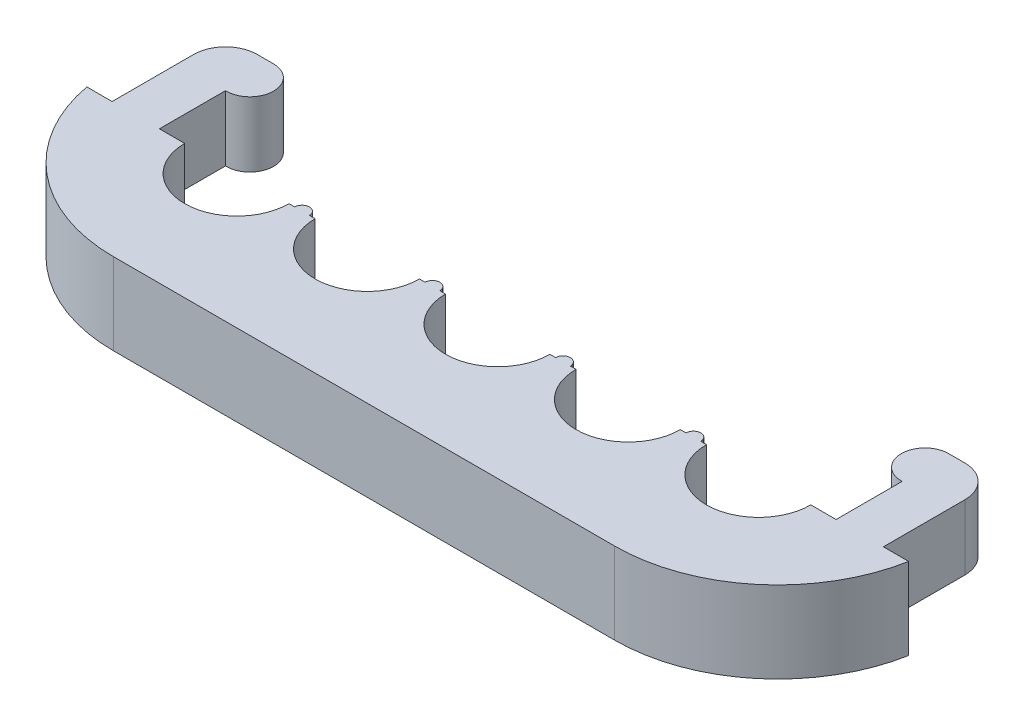
SolidWorks part; units mm, degrees
ref_plane "Plano frontal" through (0, 0, 0) normal (0, 0, 1) x (1, 0, 0)
ref_plane "Plano superior" through (0, 0, 0) normal (0, 1, 0) x (1, 0, 0)
ref_plane "Plano direito" through (0, 0, 0) normal (1, 0, 0) x (0, 0, -1)
sketch "Esboço1" plane through (0, 0, 0) normal (0, 1, 0) x (1, 0, 0)
  line L0 (-25.2, 0) -> (-19.2, 0)
  line L5 (25.2, 0) -> (25.2, -8.2)
  line L6 (25.2, -8.2) -> (-25.2, -8.2)
  line L7 (-25.2, -8.2) -> (-25.2, 0)
  line L8 (-12.8, 0) -> (-11.2, 0)
  line L9 (-4.8, 0) -> (-3.2, 0)
  line L10 (3.2, 0) -> (4.8, 0)
  line L11 (11.2, 0) -> (12.8, 0)
  line L12 (19.2, 0) -> (25.2, 0)
  arc A0 (-19.2, 0) -> (-12.8, 0) centre (-16, 0) ccw
  arc A1 (-11.2, 0) -> (-4.8, 0) centre (-8, 0) ccw
  arc A2 (-3.2, 0) -> (3.2, 0) centre (0, 0) ccw
  arc A3 (4.8, 0) -> (11.2, 0) centre (8, 0) ccw
  arc A4 (12.8, 0) -> (19.2, 0) centre (16, 0) ccw
  dimension "D1" = 6.4
  dimension "D4" = 6
  dimension "D5" = 5
  dimension "D3" = 8
  dimension "D2" = 5
extrude "Ressalto-extrusão1" add sketch "Esboço1" along normal mid plane 5
sketch "Esboço2" plane through (0, 2.5, 0) normal (0, 1, 0) x (1, 0, 0)
  line L0 (-11.2, 0) -> (-12.8, 0) construction
  line L1 (12.8, 0) -> (11.2, 0) construction
  circle A0 centre (-12, 0) radius 0.45
  circle A1 centre (-4, 0) radius 0.45
  circle A2 centre (4, 0) radius 0.45
  circle A3 centre (12, 0) radius 0.45
  point P13 (12, 0)
  dimension "D1" = 0.9
  dimension "D2" = 4
sketch "Esboço3" plane through (0, 2.5, 0) normal (0, 1, 0) x (1, 0, 0)
  line L0 (-19.2, 0) -> (-25.2, 0) construction
  line L1 (-2.75, 0) -> (2.75, 0) construction
  line L2 (-23.7, 0) -> (-20.7, 0) construction
  line L3 (-23.7, 5) -> (-23.7, -5) construction
  line L4 (-21.7, -7) -> (-20.7, -7) construction
  line L5 (-20.7, 4) -> (-20.7, -4) construction
  line L12 (-21.7, 7) -> (-20.7, 7) construction
  line L13 (-23.65, 5) -> (-23.65, 0)
  line L14 (-21.7, 6.95) -> (-20.7, 6.95)
  line L15 (-20.75, 4.0509) -> (-20.75, 0)
  line L17 (-20.75, 4.0509) -> (-20.75, -4) construction
  line L18 (-23.65, 5) -> (-23.65, -5) construction
  line L22 (0, -2.75) -> (0, 2.75) construction
  line L23 (21.7, 7) -> (20.7, 7) construction
  line L24 (-23.65, 0) -> (-20.75, 0)
  line L25 (23.7, 0) -> (20.7, 0) construction
  line L26 (23.65, 0) -> (20.75, 0)
  line L27 (20.75, 4.0509) -> (20.75, 0)
  line L28 (21.7, 6.95) -> (20.7, 6.95)
  line L29 (23.65, 5) -> (23.65, 0)
  arc A0 (-20.7, -7) -> (-20.7, -4) centre (-20.7, -5.5) ccw construction
  arc A3 (-23.7, -5) -> (-21.7, -7) centre (-21.7, -5) ccw construction
  arc A4 (-23.7, 5) -> (-21.7, 7) centre (-21.7, 5) cw construction
  arc A7 (-20.7, 7) -> (-20.7, 4) centre (-20.7, 5.5) cw construction
  arc A8 (-23.65, 5) -> (-21.7, 6.95) centre (-21.7, 5) cw
  arc A9 (-20.7, 6.95) -> (-20.75, 4.0509) centre (-20.7, 5.5) cw
  arc A12 (20.7, 7) -> (20.7, 4) centre (20.7, 5.5) ccw construction
  arc A13 (23.7, 5) -> (21.7, 7) centre (21.7, 5) ccw construction
  arc A14 (20.7, 6.95) -> (20.75, 4.0509) centre (20.7, 5.5) ccw
  arc A15 (23.65, 5) -> (21.7, 6.95) centre (21.7, 5) ccw
  point P14 (-23.7, -7)
  point P16 (-22.2, 0)
  point P17 (-22.2, 0)
  point P29 (23.7, 7)
  point P38 (-23.7, 7)
  point P50 (23.5, 5)
  point P51 (23.5, -5)
  point P56 (20.9, 4.2155)
  point P57 (20.9, -4)
  dimension "D2" = 3
  dimension "D1" = 3
  dimension "D3" = 7
  dimension "D5" = 0.05
extrude "Ressalto-extrusão2" add sketch "Esboço3" against normal blind 4
fillet "Filete1" radius 10 2 edges at (-25.2, 0, 8.2) (25.2, 0, 8.2)
extrude "Ressalto-extrusão3" add sketch "Esboço2" against normal through all
